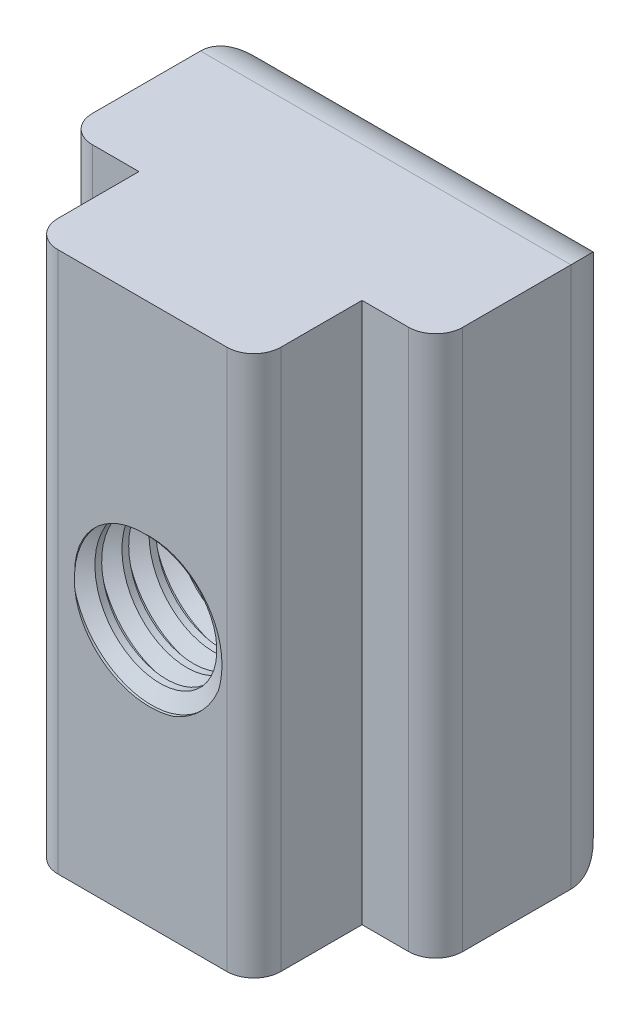
SolidWorks part; units mm, degrees
ref_plane "Front Plane" through (0, 0, 0) normal (0, 0, 1) x (1, 0, 0)
ref_plane "Top Plane" through (0, 0, 0) normal (0, 1, 0) x (1, 0, 0)
ref_plane "Right Plane" through (0, 0, 0) normal (1, 0, 0) x (0, 0, -1)
sketch "Sketch1" plane through (0, 0, 0) normal (0, 1, 0) x (1, 0, 0)
  line L1 (0, 0) -> (-8.25, 0)
  line L2 (0, 0) -> (0, 4)
  line L3 (0, 4) -> (-8.25, 4)
  line L4 (-8.25, 0) -> (-8.25, 4)
  line L5 (-10.975, 11) -> (2.725, 11)
  line L6 (-10.975, 11) -> (-10.975, 4)
  line L7 (-10.975, 4) -> (2.725, 4)
  line L8 (2.725, 11) -> (2.725, 4)
  point P9 (-4.125, 4)
  point P10 (-4.125, 4)
  dimension "D1" = 8.25
  dimension "D2" = 13.7
  dimension "D3" = 4
  dimension "D4" = 7
extrude "Boss-Extrude1" add sketch "Sketch1" along normal blind 20 contours L4 L1 L2 L3 | L8 L5 L6 L7 L3 region at (-4.125, 0, -2) region at (-4.125, 0, -7.5)
sketch "Sketch2" plane through (0, 0, 0) normal (0, 0, 1) x (1, 0, 0)
  line L0 (0, 0) -> (-8.25, 0) construction
  line L1 (-8.25, 20) -> (-8.25, 0) construction
  circle A0 centre (-4.125, 10) radius 2.5
  point P5 (-4.125, 0)
  point P8 (-8.25, 10)
  dimension "D1" = 5
extrude "Cut-Extrude1" cut sketch "Sketch2" against normal through all
thread "Thread1" pitch 1 method cut profile "Thread Profile1" start angle 0, offset 1, length 0, pitch 1, diameter 5
ref_plane "Plane1" through (-6.625, 10, 1) normal (0, -1, 0) x (-1, 0, 0)
sketch "Thread Profile1" plane through (-6.625, 10, 1) normal (0, -1, 0) x (-1, 0, 0)
  line L0 (0, 0) -> (0, 1) construction
  line L1 (0, 0) -> (0.5413, 0.3125)
  line L2 (0.5413, 0.3125) -> (0.5413, 0.4375)
  line L3 (0.5413, 0.4375) -> (0, 0.75)
  line L4 (0.5413, 0.375) -> (0, 0.375) construction
  line L11 (0, 0) -> (0, 0.75)
  point P2 (0, 0)
  dimension "Pitch" = 1
  dimension "Profile_Angle" = 60
  dimension "Profile_Land" = 0.125
  dimension "Profile_Height" = 0.5413
fillet "Fillet1" radius 2 4 edges at (-4.125, 20, -11) (-4.125, 0, -11) (2.725, 10, -11) (-10.975, 10, -11)
fillet "Fillet2" radius 1 4 edges at (2.725, 10, -4) (0, 10, 0) (-8.25, 10, 0) (-10.975, 10, -4)
